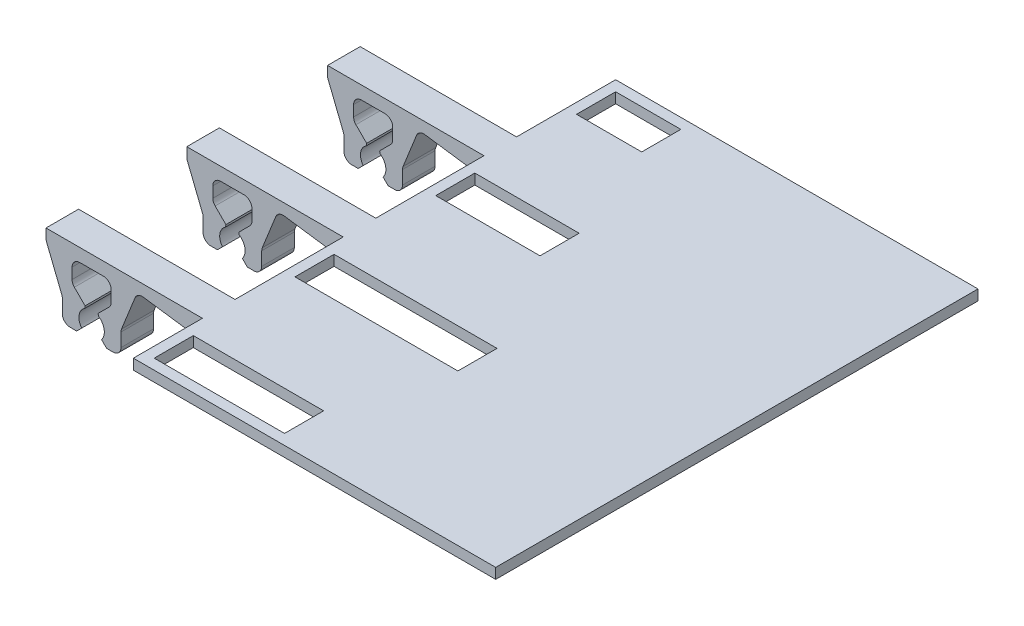
SolidWorks part; units mm, degrees
note: '?' marks a value the reader was unsure of.
ref_plane "Front Plane" through (0, 0, 0) normal (0, 0, 1) x (1, 0, 0)
ref_plane "Top Plane" through (0, 0, 0) normal (0, 1, 0) x (1, 0, 0)
ref_plane "Right Plane" through (0, 0, 0) normal (1, 0, 0) x (0, 0, -1)
sketch "Sketch1" plane through (0, 0, 0) normal (0, 1, 0) x (1, 0, 0)
  line L1 (-27.8, -37) -> (27.8, -37)
  line L2 (-27.8, -37) -> (-27.8, 37)
  line L3 (-27.8, 37) -> (27.8, 37)
  line L4 (27.8, -37) -> (27.8, 37)
  line L5 (-27.8, -37) -> (27.8, 37) construction
  line L6 (-27.8, 37) -> (27.8, -37) construction
  point P0 (0, 0)
  dimension "D1" = 55.6
  dimension "D2" = 74
extrude "plate" add sketch "Sketch1" along normal blind 1.6
sketch "Sketch5" plane through (0, 1.6, 0) normal (0, 1, 0) x (1, 0, 0)
  line L0 (2, 13.8) -> (-24.2, 13.8) construction
  line L1 (-26.2, 29.4) -> (-16.2, 29.4)
  line L2 (-26.2, 29.4) -> (-26.2, 35.4)
  line L3 (-26.2, 35.4) -> (-16.2, 35.4)
  line L4 (-16.2, 29.4) -> (-16.2, 35.4)
  line L5 (-27.8, 37) -> (-27.8, -37) construction
  line L6 (-10.2, 13.8) -> (-26.2, 13.8)
  line L7 (27.8, 37) -> (-27.8, 37) construction
  line L8 (-10.2, 13.8) -> (-10.2, 7.8)
  line L9 (-10.2, 7.8) -> (-26.2, 7.8)
  line L10 (-26.2, 13.8) -> (-26.2, 7.8)
  line L12 (-1.2, -13.8) -> (-26.2, -13.8)
  line L13 (-1.2, -13.8) -> (-1.2, -7.8)
  line L14 (-1.2, -7.8) -> (-26.2, -7.8)
  line L15 (-26.2, -13.8) -> (-26.2, -7.8)
  line L16 (2, -7.8) -> (-18, -7.8) construction
  line L17 (2, -29.4) -> (-18, -29.4) construction
  line L18 (-6.2, -29.4) -> (-26.2, -29.4)
  line L19 (-6.2, -29.4) -> (-6.2, -35.4)
  line L20 (-6.2, -35.4) -> (-26.2, -35.4)
  line L21 (-26.2, -29.4) -> (-26.2, -35.4)
  dimension "D1" = 10
  dimension "D2" = 6
  dimension "D3" = 1.6
  dimension "D4" = 1.6
  dimension "D5" = 16
  dimension "D6" = 25
  dimension "D7" = 20
extrude "air window" cut sketch "Sketch5" against normal blind 1.6
ref_plane "slot end 1" through (0, 0, -29.4) normal (0, 0, -1) x (-1, 0, 0)
ref_plane "slot start 2" through (0, 0, -13.8) normal (0, 0, 1) x (1, 0, 0)
ref_plane "Plane3" through (0, 0, -16.8) normal (0, 0, 1) x (1, 0, 0)
ref_plane "rod plane" through (0, -8, 0) normal (0, -1, 0) x (-1, 0, 0)
sketch "locate rods" plane through (0, 0, 0) normal (0, 0, 1) x (1, 0, 0)
  line L0 (-30.58, -8) -> (30.58, -8) construction
  line L1 (-27.8, 1.6) -> (-27.8, 0) construction
  point P0 (-44.8, -8)
  point P1 (13.2, -8)
  dimension "D1" = 58
  dimension "D2" = 17
ref_axis "front rod" through (-44.8, -8, 0) along (0, 0, 1)?
ref_axis "back rod" through (13.2, -8, 0) along (0, 0, 1)?
sketch "Sketch9" plane through (0, -8, 0) normal (0, -1, 0) x (-1, 0, 0)
  line L0 (44.8, 0) -> (-13.2, 0) construction
  line L1 (44.8, 0) -> (44.8, -20.1912) construction
  line L2 (-13.2, 0) -> (-13.2, -20.1912) construction
  point P9 (15.8, 0)
ref_plane "mid rods" through (-15.8, -8, 0) normal (1, 0, 0) x (0, 0, -1)
sketch "Sketch11" plane through (0, 0, 0) normal (0, -1, 0) x (1, 0, 0)
  line L0 (27.8, -37) -> (-27.8, -37) construction
  line L1 (21.8, 34) -> (4.6, 34)
  line L2 (24.8, 31) -> (24.8, -31)
  line L3 (21.8, -34) -> (4.6, -34)
  line L4 (1.6, 31) -> (1.6, -31)
  line L5 (24.8, 34) -> (1.6, -34) construction
  line L6 (24.8, -34) -> (1.6, 34) construction
  line L7 (27.8, 37) -> (27.8, -37) construction
  arc A0 (21.8, 34) -> (24.8, 31) centre (21.8, 31) cw
  arc A1 (4.6, 34) -> (1.6, 31) centre (4.6, 31) ccw
  arc A2 (4.6, -34) -> (1.6, -31) centre (4.6, -31) cw
  arc A3 (24.8, -31) -> (21.8, -34) centre (21.8, -31) cw
  point P0 (13.2, 0)
  dimension "D3" = 3
  dimension "D1" = 3
  dimension "D2" = 3
extrude "clip thin" cut sketch "Sketch11" against normal blind 0.4
sketch "Sketch6" plane through (0, 0, -16.8) normal (0, 0, 1) x (1, 0, 0)
  line L5 (-37.8, 0) -> (-40.3, -6.25)
  line L7 (8.7, -6.25) -> (-40.3, -6.25) construction
  line L11 (13.2, -9.75) -> (13.2, 1.6) construction
  line L12 (-27.8, 0) -> (27.8, 0) construction
  line L13 (-49.3, -9.75) -> (-40.3, -9.75)
  line L14 (-44.8, -9.75) -> (-44.8, 1.6) construction
  line L16 (-49.3, -8) -> (-44.8, -8) construction
  line L17 (5.56, 1.6) -> (20.84, 1.6)
  line L27 (-37.8, 1.6) -> (-17.8, 1.6)
  line L28 (21.8, 0) -> (24.8, 0) construction
  line L29 (-40.3, -6.25) -> (-40.3, -9.75)
  line L30 (-49.3, -6.25) -> (-49.3, -9.75)
  line L31 (-51.8, 0) -> (-49.3, -6.25)
  line L32 (-51.8, 1.6) -> (-51.8, 0)
  line L34 (20.84, 1.6) -> (17.7, -6.25)
  line L35 (17.7, -6.25) -> (17.7, -9.75)
  line L36 (8.7, -6.25) -> (8.7, -9.75)
  line L37 (17.7, -9.75) -> (8.7, -9.75)
  line L38 (5.56, 1.6) -> (8.7, -6.25)
  line L44 (-51.8, 1.6) -> (-37.8, 1.6)
  line L47 (-27.8, 1.6) -> (27.8, 1.6) construction
  line L48 (-17.8, 1.6) -> (-17.8, 0)
  line L49 (-17.8, 0) -> (-27.8, -1.4)
  line L50 (-27.8, -1.4) -> (-37.8, 0)
  line L51 (-37.8, 0) -> (-37.8, 1.6) construction
  line L52 (-27.8, 1.6) -> (-27.8, -1.4) construction
  point P53 (-44.8, -8)
  dimension "D1" = 3
  dimension "D4" = 9
  dimension "D5" = 3.5
  dimension "D6" = 2.5
extrude "clips" add sketch "Sketch6" against normal blind 5
sketch "Sketch7" plane through (0, 0, -16.8) normal (0, 0, 1) x (1, 0, 0)
  line L0 (-46.3, -9.75) -> (-43.3, -9.75)
  line L1 (-49.3, -9.75) -> (-40.3, -9.75) construction
  line L2 (-46.3, -9.75) -> (-45.8, -5.75)
  line L3 (-45.8, -5.75) -> (-47.8, -3.75)
  line L6 (-41.8, -0.4) -> (-41.8, -3.75)
  line L7 (-41.8, -3.75) -> (-43.8, -5.75)
  line L8 (-43.8, -5.75) -> (-43.3, -9.75)
  line L9 (-44.9448, 0) -> (24.1674, 0) construction
  line L10 (13.2, 0.4) -> (13.2, -9.75) construction
  line L27 (10.2, -3.75) -> (16.2, -3.75) construction
  line L28 (-41.8, -3.75) -> (-47.8, -3.75) construction
  line L29 (-44.8, 0) -> (-44.8, -9.75) construction
  line L30 (12.2, -5.75) -> (11.7, -9.75)
  line L31 (10.2, -3.75) -> (12.2, -5.75)
  line L32 (10.2, 0.4) -> (10.2, -3.75)
  line L33 (16.2, 0.4) -> (10.2, 0.4)
  line L34 (16.2, -3.75) -> (16.2, 0.4)
  line L35 (14.2, -5.75) -> (16.2, -3.75)
  line L36 (14.7, -9.75) -> (14.2, -5.75)
  line L37 (14.7, -9.75) -> (11.7, -9.75)
  line L38 (-27.8, 1.6) -> (-51.8, 1.6) construction
  line L39 (-17.8, 0) -> (-27.8, 0) construction
  line L40 (-45.8, -5.75) -> (-43.8, -5.75) construction
  line L41 (-41.8, -0.4) -> (-47.8, -0.4)
  line L42 (-47.8, -0.4) -> (-47.8, -3.75)
  line L43 (20.36, 0.4) -> (6.04, 0.4) construction
  point P4 (-44.8, -9.75)
  point P8 (-44.8, -3.75)
  dimension "D1" = 3
  dimension "D2" = 6
  dimension "D3" = 4
  dimension "D4" = 2
  dimension "D5" = 45
  dimension "D6" = 2
extrude "clip cut1" cut sketch "Sketch7" against normal blind 10
sketch "Sketch8" plane through (0, 0, -16.8) normal (0, 0, 1) x (1, 0, 0)
  line L0 (-46.05, -7.75) -> (-43.55, -7.75) construction
  line L1 (-45.8, -5.75) -> (-46.3, -9.75) construction
  line L2 (-43.3, -9.75) -> (-43.8, -5.75) construction
  circle A0 centre (-44.8, -7.75) radius 1.95
  circle A1 centre (13.2, -8) radius 1.95
  dimension "D1" = 3.9
extrude "clip cut2" cut sketch "Sketch8" against normal through all
fillet "Fillet1" radius 1.2 24 edges at (-49.3, -9.75, -19.3) (-51.8, 0, -19.3) (-49.3, -6.25, -19.3) (-41.8, -3.75, -19.3) (-40.3, -9.75, -19.3) (-40.3, -6.25, -19.3) (8.7, -9.75, -19.3) (17.7, -9.75, -19.3) (17.7, -6.25, -19.3) (8.7, -6.25, -19.3) (16.2, -3.75, -19.3) (10.2, -3.75, -19.3) (16.2, 0.4, -19.3) (10.2, 0.4, -19.3) (-47.8, -3.75, -19.3) (-41.8, -0.4, -19.3) (-47.8, -0.4, -19.3) (-37.8, 0, -19.3) (8.12, 0.4, -21.8) (18.28, 0.4, -21.8) (18.28, 0.4, -16.8) (8.12, 0.4, -16.8) (6.04, 0.4, -19.3) (20.36, 0.4, -19.3)
chamfer "Chamfer1" distance 0.8 angle 45 4 edges at (-46.3, -9.75, -19.3) (-43.3, -9.75, -19.3) (11.7, -9.75, -19.3) (14.7, -9.75, -19.3)
pattern_linear "LPattern1" count 3 spacing 21.6 along (0, 0, 1) of "clips", "clip cut1", "clip cut2", "Fillet1", "Chamfer1"
